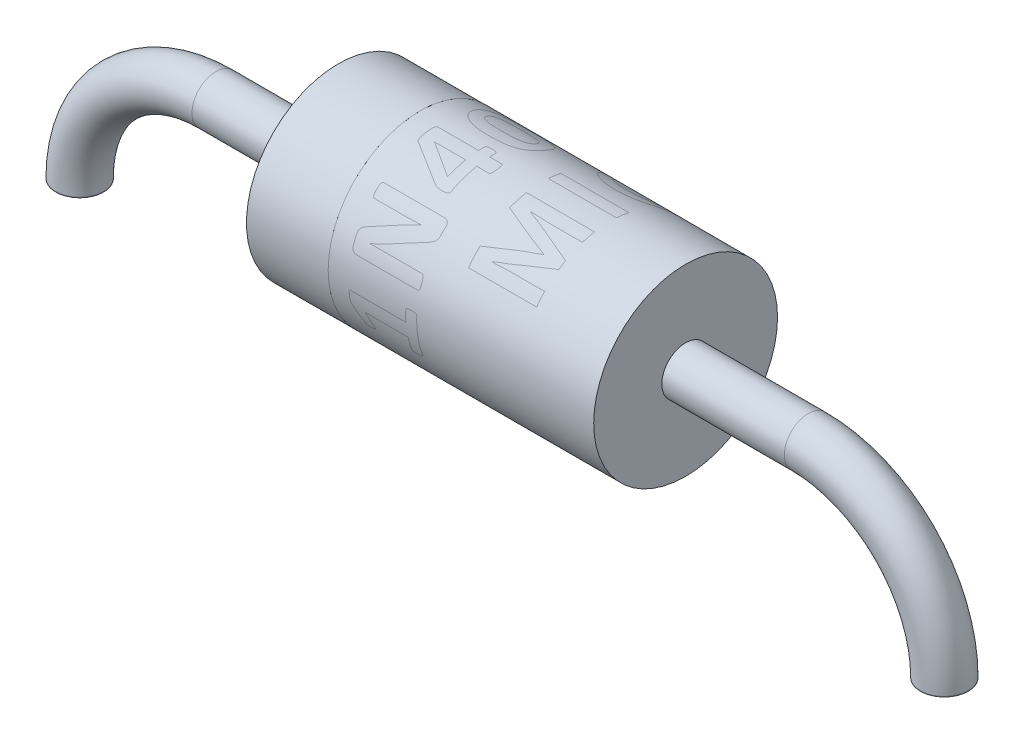
SolidWorks part; units mm, degrees
other "Diode"
other "Cathode Silver Band"
other "Wire"
ref_plane "Front Plane" through (0, 0, 0) normal (0, 0, 1) x (1, 0, 0)
ref_plane "Top Plane" through (0, 0, 0) normal (0, 1, 0) x (1, 0, 0)
ref_plane "Right Plane" through (0, 0, 0) normal (1, 0, 0) x (0, 0, -1)
sketch "Sketch1" plane through (0, 0, 0) normal (1, 0, 0) x (0, 0, -1)
  circle A0 centre (0, 0) radius 1.35
  circle A1 centre (0, 0) radius 0.35
  dimension "D1" = 2.7
  dimension "D2" = 0.7
extrude "Boss-Extrude1" add sketch "Sketch1" along normal mid plane 5.1
sketch "Sketch2" plane through (-2.55, 0, 0) normal (-1, 0, 0) x (0, 0, 1)
  circle A1 centre (0, 0) radius 1.35 construction
  circle A2 centre (0, 0) radius 1.34
  circle A3 centre (0, 0) radius 1.34
  circle A4 centre (0, 0) radius 1.35
  dimension "D1" = 0.01
extrude "Cut-Extrude1" cut sketch "Sketch2" against normal blind 1.2
sketch "Sketch3" plane through (-1.35, 0, 0) normal (-1, 0, 0) x (0, 0, 1)
  circle A0 centre (0, 0) radius 1.34 construction
  circle A1 centre (0, 0) radius 1.34
  circle A2 centre (0, 0) radius 1.35 construction
  circle A3 centre (0, 0) radius 1.35
extrude "Boss-Extrude2" add sketch "Sketch3" along normal up to surface (1.2 mm away) separate body up to face at (-2.55, 0, -0.35)
ref_plane "Plane1" through (0, 5, 0) normal (0, 1, 0) x (1, 0, 0)
sketch "Sketch4" plane through (0, 5, 0) normal (0, 1, 0) x (1, 0, 0)
  line L0 (-0.05, 7.5) -> (-0.05, -7.5) construction
  line L1 (-0.05, 0) -> (-2.55, 0) construction
  line L2 (-2.55, 1.35) -> (-2.55, -1.35) construction
  line L4 (-0.05, 0) -> (1.45, 0) construction
  line L5 (1.45, 7.5) -> (1.45, -7.5) construction
  text T0 "1N4007" font "Calibri" height 1
  text T1 "MIC" font "Corbel" height 1
  dimension "D1" = 2.5
  dimension "D2" = 15
  dimension "D3" = 1.5
wrap "Wrap1" sketch "Sketch4" wrap type scribe source sketch "Sketch4" face at (2.55, 0, -1.35)
sketch "Sketch5" plane through (0, 0, 0) normal (0, 0, 1) x (1, 0, 0)
  line L0 (0, 0) -> (-4.35, 0)
  line L1 (-6.35, -2) -> (-6.35, -23.5084)
  line L2 (0, 0) -> (4.35, 0)
  line L3 (6.35, -2) -> (6.35, -23.5084)
  arc A0 (-4.35, 0) -> (-6.35, -2) centre (-4.35, -2) ccw
  arc A1 (4.35, 0) -> (6.35, -2) centre (4.35, -2) cw
  dimension "D2" = 2
  dimension "D3" = 58
  dimension "D1" = 12.7
sketch "Sketch6" plane through (0, 0, 0) normal (1, 0, 0) x (0, 0, -1)
  circle A0 centre (0, 0) radius 0.35
  dimension "D1" = 0.7
sweep "Sweep1" add profiles "Sketch6" path "Sketch5"
sketch "Skizze1" plane through (0, -23.5084, 0) normal (0, -1, 0) x (1, 0, 0)
  line L1 (-8.607, 2.6564) -> (8.0585, 2.6564)
  line L2 (-8.607, 2.6564) -> (-8.607, -4.2953)
  line L3 (-8.607, -4.2953) -> (8.0585, -4.2953)
  line L4 (8.0585, 2.6564) -> (8.0585, -4.2953)
extrude "Schnitt-Linear austragen1" cut sketch "Skizze1" against normal blind 21.5
